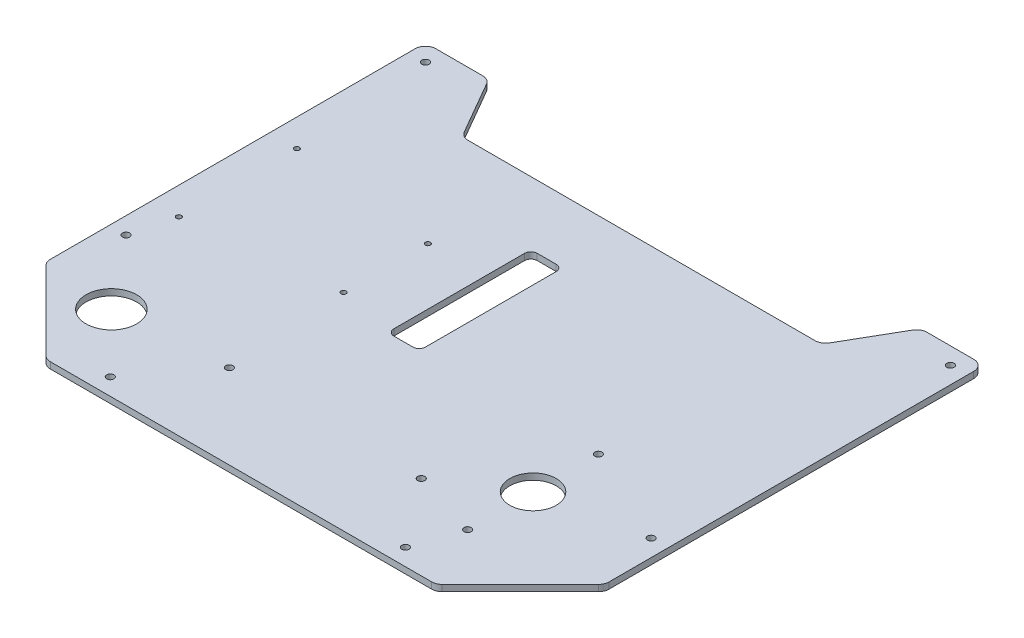
SolidWorks part; units mm, degrees
material "Acier non allié"
ref_plane "Front" through (0, 0, 0) normal (0, 0, 1) x (1, 0, 0)
ref_plane "Top" through (0, 0, 0) normal (0, 1, 0) x (1, 0, 0)
ref_plane "Right" through (0, 0, 0) normal (1, 0, 0) x (0, 0, -1)
sketch "Esquisse1" plane through (0, 0, 0) normal (0, 1, 0) x (1, 0, 0)
  line L0 (0, 0) -> (0, 1919.0564) construction
  line L1 (-92.5, 0) -> (92.5, 0)
  line L2 (92.5, 0) -> (132.5, 40)
  line L3 (132.5, 40) -> (132.5, 220)
  line L4 (132.5, 220) -> (102.5, 220)
  line L5 (102.5, 220) -> (85.1795, 190)
  line L6 (85.1795, 190) -> (-85.1795, 190)
  line L7 (-102.5, 220) -> (-85.1795, 190)
  line L8 (-132.5, 220) -> (-102.5, 220)
  line L9 (-132.5, 40) -> (-132.5, 220)
  line L10 (-92.5, 0) -> (-132.5, 40)
  point P12 (0, 190)
  dimension "D1" = 132.5
  dimension "D2" = 220
  dimension "D3" = 30
  dimension "D4" = 30
  dimension "D5" = 40
  dimension "D6" = 40
  dimension "D7" = 60
extrude "Boss.-Extru.1" add sketch "Esquisse1" along normal blind 3
fillet "Congé1" radius 5 10 edges at (132.5, 1.5, -220) (102.5, 1.5, -220) (85.1795, 1.5, -190) (-85.1795, 1.5, -190) (-102.5, 1.5, -220) (-132.5, 1.5, -220) (-132.5, 1.5, -40) (-92.5, 1.5, 0) (92.5, 1.5, 0) (132.5, 1.5, -40)
sketch "Esquisse2" plane through (0, 0, 0) normal (0, -1, 0) x (1, 0, 0)
  line L0 (0, 0) -> (0, -330.9968) construction
  line L1 (-90.4289, 0) -> (90.4289, 0) construction
  line L2 (-105.3868, -220) -> (-127.5, -220) construction
  line L3 (-132.5, -215) -> (-132.5, -42.0711) construction
  circle A0 centre (-70, -8) radius 1
  circle A1 centre (-124.5, -70) radius 1
  circle A2 centre (-124.5, -212) radius 1
  circle A3 centre (124.5, -212) radius 1
  circle A4 centre (124.5, -70) radius 1
  circle A5 centre (70, -8) radius 1
  dimension "D3" = 2
  dimension "D6" = 2
  dimension "D9" = 2
  dimension "D1" = 70
  dimension "D2" = 8
  dimension "D4" = 124.5
  dimension "D5" = 70
  dimension "D7" = 8
  dimension "D8" = 8
extrude "Enlèv. mat.-Extru.1" cut sketch "Esquisse2" against normal through all
hole_wizard "Dégagement M31" positions "Esquisse3" profile "Esquisse4" hole size "M3" standard "ISO" end condition through all
sketch "Esquisse3" plane through (0, 0, 0) normal (0, -1, 0) x (-1, 0, 0)
  point P0 (-70, 8)
  point P3 (-124.5, 70)
  point P6 (-124.5, 212)
  point P9 (124.5, 212)
  point P12 (124.5, 70)
  point P15 (70, 8)
sketch "Esquisse4" plane through (70, 0, -8) normal (1, 0, 0) x (0, 0, -1)
  line L0 (0, 0) -> (0, 3)
  line L1 (0, 3) -> (1.7, 3)
  line L2 (1.7, 3) -> (1.7, 0)
  line L5 (1.7, 0) -> (0, 0)
  line L11 (0, -6.35) -> (0, 107.95) construction
  dimension "Diamètre du perçage jusqu'au prochain" = 3.4
  dimension "Profondeur du perçage jusqu'au prochain" = 3
sketch "Esquisse5" plane through (0, 0, 0) normal (0, -1, 0) x (1, 0, 0)
  line L0 (-119.5, -146) -> (-119.5, -90) construction
  line L5 (-49.39, -138) -> (-49.39, -98) construction
  line L6 (132.5, -42.0711) -> (132.5, -215) construction
  line L7 (77.5, -92) -> (77.5, -30) construction
  line L20 (-132.5, -215) -> (-132.5, -42.0711) construction
  line L21 (-90.4289, 0) -> (90.4289, 0) construction
  line L22 (-105.3868, -220) -> (-127.5, -220) construction
  line L23 (-22.5, -160) -> (-7.5, -160)
  line L24 (-22.5, -160) -> (-22.5, -92)
  line L25 (-22.5, -92) -> (-7.5, -92)
  line L26 (-7.5, -160) -> (-7.5, -92)
  line L27 (-45.5, -40) -> (45.5, -40) construction
  circle A0 centre (-97.5, -36) radius 12
  circle A1 centre (-45.5, -40) radius 1.5
  circle A2 centre (45.5, -40) radius 1.5
  circle A3 centre (77.5, -61) radius 11
  circle A4 centre (77.5, -92) radius 1.5
  circle A5 centre (77.5, -30) radius 1.5
  circle A6 centre (-119.5, -146) radius 1
  circle A7 centre (-119.5, -90) radius 1
  circle A8 centre (-49.39, -138) radius 1
  circle A9 centre (-49.39, -98) radius 1
  point P8 (77.5, -61)
  point P18 (-119.5, -118)
  point P35 (-22.5, -126)
  dimension "D10" = 24
  dimension "D15" = 3
  dimension "D16" = 3
  dimension "D2" = 22
  dimension "D6" = 3
  dimension "D7" = 3
  dimension "D20" = 2
  dimension "D21" = 2
  dimension "D27" = 2
  dimension "D28" = 2
  dimension "D3" = 55
  dimension "D4" = 61
  dimension "D5" = 62
  dimension "D8" = 35
  dimension "D9" = 36
  dimension "D11" = 60
  dimension "D12" = 68
  dimension "D13" = 110
  dimension "D14" = 15
  dimension "D17" = 91
  dimension "D18" = 40
  dimension "D19" = 87
  dimension "D22" = 102
  dimension "D23" = 13
  dimension "D24" = 56
  dimension "D25" = 8
  dimension "D26" = 40
  dimension "D29" = 70.11
extrude "Enlèv. mat.-Extru.2" cut sketch "Esquisse5" against normal through all
fillet "Congé2" radius 3 4 edges at (-22.5, 1.5, -92) (-7.5, 1.5, -92) (-7.5, 1.5, -160) (-22.5, 1.5, -160)
hole_wizard "Dégagement M32" positions "Esquisse6" profile "Esquisse7" hole size "M3" standard "ISO" end condition up to next
sketch "Esquisse6" plane through (0, 3, 0) normal (0, 1, 0) x (1, 0, 0)
  point P0 (-45.5, 40)
  point P3 (45.5, 40)
  point P7 (77.5, 92)
  point P10 (77.5, 30)
sketch "Esquisse7" plane through (-45.5, 3, -40) normal (1, 0, 0) x (0, 0, 1)
  line L0 (0, 0) -> (0, 3)
  line L1 (0, 3) -> (1.7, 3)
  line L2 (1.7, 3) -> (1.7, 0)
  line L5 (1.7, 0) -> (0, 0)
  line L11 (0, -6.35) -> (0, 107.95) construction
  dimension "Diamètre du perçage jusqu'au prochain" = 3.4
  dimension "Profondeur du perçage jusqu'au prochain" = 3
hole_wizard "Dégagement M21" positions "Esquisse8" profile "Esquisse9" hole size "M2" standard "ISO" end condition up to next
sketch "Esquisse8" plane through (0, 3, 0) normal (0, 1, 0) x (1, 0, 0)
  point P0 (-119.5, 146)
  point P3 (-119.5, 90)
  point P6 (-49.39, 98)
  point P9 (-49.39, 138)
sketch "Esquisse9" plane through (-119.5, 3, -146) normal (1, 0, 0) x (0, 0, 1)
  line L0 (0, 0) -> (0, 3)
  line L1 (0, 3) -> (1.2, 3)
  line L2 (1.2, 3) -> (1.2, 0)
  line L5 (1.2, 0) -> (0, 0)
  line L11 (0, -6.35) -> (0, 107.95) construction
  dimension "Diamètre du perçage jusqu'au prochain" = 2.4
  dimension "Profondeur du perçage jusqu'au prochain" = 3
equation "\"WIDTH\"= 300mm'Total width of the robot"
equation "\"LENGTH\"= 220mm'Total length of the robot"
equation "\"CUT_DEPTH\"= 45mm'Depth of the cut on the edges of the plate"
equation "\"Plate_th\"= 3mm'Thickness of the plate"
equation "\"D1\"= \"Plate_th\""
